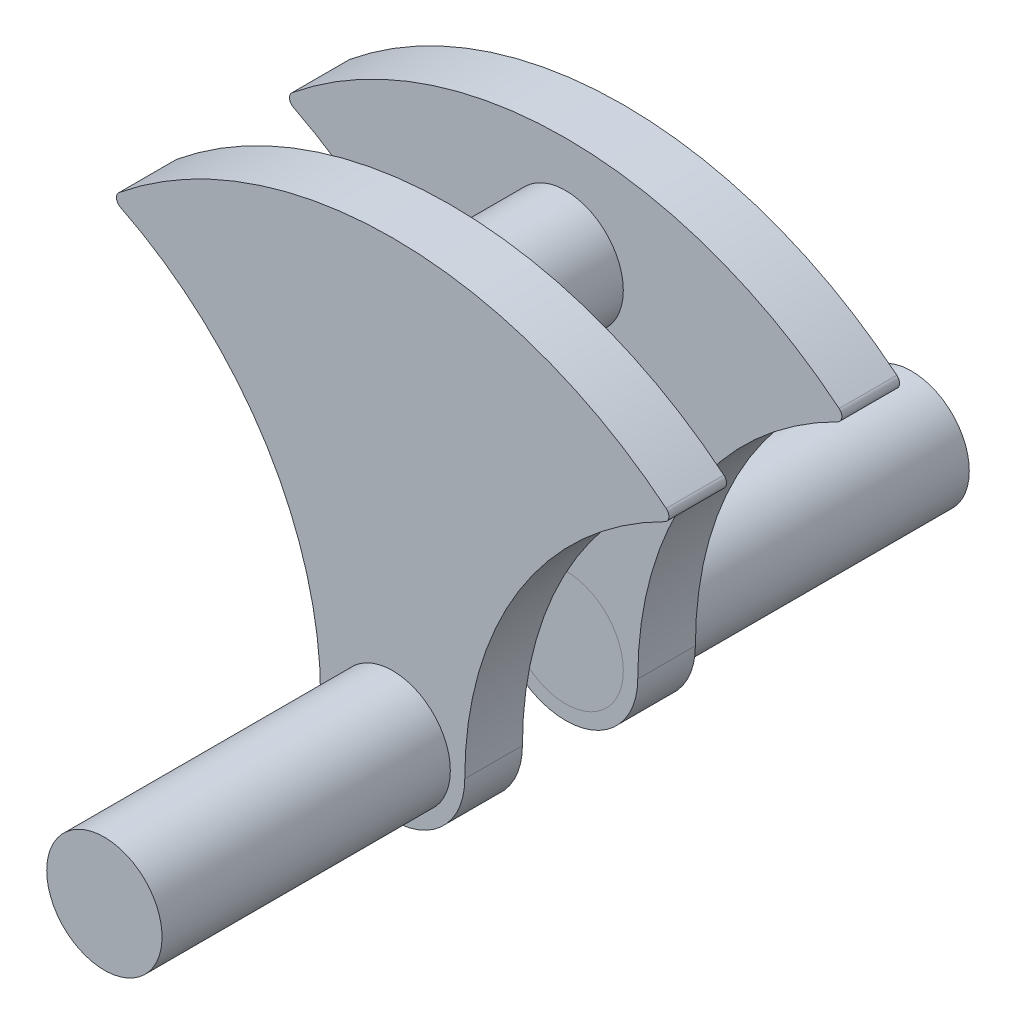
SolidWorks part; units mm, degrees
ref_plane "Front Plane" through (0, 0, 0) normal (0, 0, 1) x (1, 0, 0)
ref_plane "Top Plane" through (0, 0, 0) normal (0, 1, 0) x (1, 0, 0)
ref_plane "Right Plane" through (0, 0, 0) normal (1, 0, 0) x (0, 0, -1)
sketch "Sketch1" plane through (0, 0, 0) normal (0, 0, 1) x (1, 0, 0)
  line L0 (0, 0) -> (0, 189.8704) construction
  arc A0 (94.8664, 116.1911) -> (-94.8664, 116.1911) centre (0, 0) ccw
  arc A1 (-25, 0) -> (25, 0) centre (0, 0) ccw
  arc A2 (94.39, 111.9488) -> (25, 0) centre (150, 0) ccw
  arc A3 (-25, 0) -> (-94.39, 111.9488) centre (-150, 0) ccw
  circle A4 centre (0, 0) radius 20
  arc A5 (94.39, 111.9488) -> (94.8664, 116.1911) centre (93.26, 114.2236) ccw
  arc A6 (-94.39, 111.9488) -> (-94.8664, 116.1911) centre (-93.26, 114.2236) cw
  circle A7 centre (0, 114.2236) radius 20
  dimension "D1" = 2.54
  dimension "D2" = 40
  dimension "D3" = 25
  dimension "D4" = 125
  dimension "D5" = 125
  dimension "D6" = 150
extrude "Boss-Extrude1" add sketch "Sketch1" along normal blind 20
ref_plane "Plane4" through (0, 0, 40) normal (0, 0, 1) x (1, 0, 0)
extrude "Boss-Extrude5" add sketch "Sketch1<5>" along normal blind 80 contours A7 L0 | L0 A7 region at (-8.4883, 114.2236, 0) region at (8.4883, 114.2236, 0)
sketch "Sketch1<5>" plane through (0, 0, 0) normal (0, 0, 1) x (1, 0, 0) same geometry as "Sketch1"
mirror "Mirror4" about plane through (0, 0, 40) normal (0, 0, 1) of "Boss-Extrude1"
extrude "Boss-Extrude6" add sketch "Sketch1<7>" against normal blind 100 and the other way blind 20 separate body contours A4 region at (0, 0, 0)
sketch "Sketch1<7>" plane through (0, 0, 0) normal (0, 0, 1) x (1, 0, 0) same geometry as "Sketch1"
sketch "Sketch2" plane through (0, 0, 60) normal (0, 0, -1) x (-1, 0, 0)
  circle A0 centre (0, 0) radius 20
extrude "Boss-Extrude7" add sketch "Sketch2" against normal blind 120
ref_plane "Plane5" through (0, 0, 190) normal (0, 0, 1) x (1, 0, 0)
